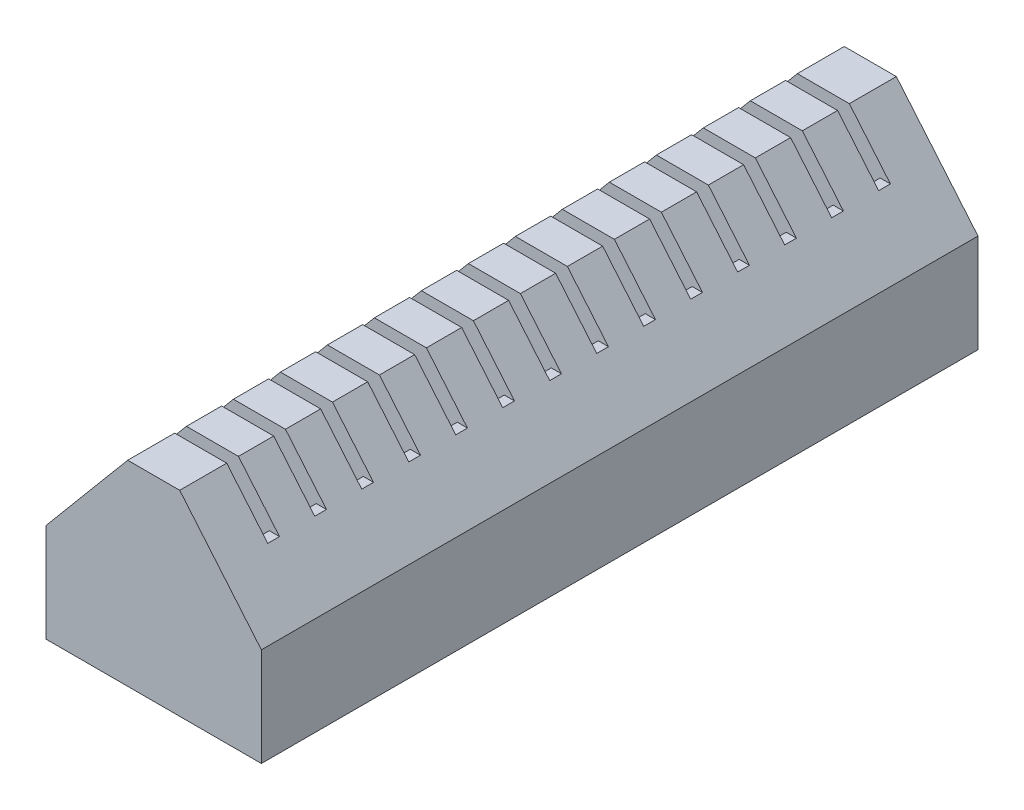
SolidWorks part; units mm, degrees
ref_plane "Ebene vorne" through (0, 0, 0) normal (0, 0, 1) x (1, 0, 0)
ref_plane "Ebene oben" through (0, 0, 0) normal (0, 1, 0) x (1, 0, 0)
ref_plane "Ebene rechts" through (0, 0, 0) normal (1, 0, 0) x (0, 0, -1)
sketch "Skizze3" plane through (0, 0, 0) normal (0, 0, 1) x (1, 0, 0)
  line L1 (0, 9.2) -> (0, -9.2) construction
  line L3 (-7.5, 0) -> (49992.5, 0) construction
  line L4 (-11, -3) -> (-11, 7.0579)
  line L5 (-11, 7.0579) -> (-2.6576, 17)
  line L6 (-2.6576, 17) -> (2.6576, 17)
  line L7 (2.6576, 17) -> (11, 7.0579)
  line L12 (0, 0) -> (8, 0) construction
  line L16 (11, 7.0579) -> (11, -3)
  line L18 (-11, -3) -> (11, -3)
  line L19 (8, 0) -> (8, 5.966) construction
  line L20 (8, 5.966) -> (0, 15.5) construction
  line L22 (0, 15.5) -> (-8, 5.966) construction
  line L23 (-8, 5.966) -> (-8, 0) construction
  line L24 (-8, 0) -> (0, 0) construction
  point P4 (0, 0)
  point P7 (0, 9.5114)
  point P16 (8.4307, 6.7411)
  point P19 (0, 0)
  point P20 (0, 15.4842)
  point P21 (0, 9.0697)
  point P23 (0, 0)
  point P24 (0, 15.6943)
  point P25 (11, 3)
  point P26 (0, 0)
  point P27 (11, 5.4655)
  point P28 (0, 0)
  dimension "D2" = 22
  dimension "D3" = 3
  dimension "D4" = 1.5
  dimension "D5" = 20
  dimension "D1" = 50
  dimension "D6" = 3
  dimension "D7" = 3
extrude "Aufsatz-Linear austragen2" add sketch "Skizze3" along normal mid plane 3.6
sketch "Skizze2" plane through (0, 0, 0) normal (0, 0, 1) x (1, 0, 0)
  line L1 (0, 9) -> (0, -9) construction
  line L3 (-7.5, 0) -> (49992.5, 0) construction
  line L20 (-8, 0) -> (8, 0)
  line L21 (8, 0) -> (8, 5.966)
  line L22 (8, 5.966) -> (1.2586, 14)
  line L23 (1.2586, 14) -> (-1.2586, 14)
  line L24 (-1.2586, 14) -> (-8, 5.966)
  line L25 (-8, 5.966) -> (-8, 0)
  line L26 (-8, 0) -> (8, 0)
  line L27 (8, 0) -> (8, 5.966)
  line L28 (8, 5.966) -> (0, 15.5)
  line L30 (0, 15.5) -> (-8, 5.966)
  line L31 (-8, 5.966) -> (-8, 0)
  point P2 (-0.7364, 14.6224)
  point P5 (0.7083, 14.6224)
  dimension "D1" = 3
extrude "Schnitt-Linear austragen1" cut sketch "Skizze2" against normal mid plane 1
sketch "Skizze5" plane through (0, 0, 0) normal (0, 0, 1) x (1, 0, 0)
  line L4 (-7.5519, 0) -> (-50007.5519, 0) construction
  line L5 (-8, 5.966) -> (-8, 0)
  line L6 (-8, 5.966) -> (-8, 0) construction
  line L7 (-8, 0) -> (8, 0)
  line L8 (-8, 0) -> (8, 0) construction
  line L9 (8, 0) -> (8, 5.966)
  line L15 (-0.75, 0) -> (0, 0.8938)
  line L16 (0, 0.8938) -> (0.75, 0)
  line L17 (0.75, 0) -> (-0.75, 0) construction
  line L18 (0, 0) -> (0, -50000) construction
  line L20 (8, 0) -> (8, 5.966) construction
  line L21 (8, 5.966) -> (0, 15.5)
  line L22 (8, 5.966) -> (0, 15.5) construction
  line L23 (0, 15.5) -> (-8, 5.966)
  line L24 (0, 15.5) -> (-8, 5.966) construction
  line L26 (-0.75, 0) -> (-0.75, -1.5)
  line L27 (-0.75, -1.5) -> (0.75, -1.5)
  line L28 (0.75, 0) -> (0.75, -1.5)
  dimension "D2" = 1.5
  dimension "D3" = 1.5
  dimension "D1" = 0
extrude "Schnitt-Linear austragen2" cut sketch "Skizze5" against normal through all both and the other way through all
sketch "Skizze6" plane through (0, 0, 1.8) normal (0, 0, 1) x (1, 0, 0)
  line L0 (0, 0) -> (0, -50000) construction
  line L1 (0, 0) -> (50000, 0) construction
  line L21 (-6.8531, 12) -> (-5.8087, 12)
  line L22 (-2.6576, 17) -> (-11, 7.0579) construction
  line L23 (-5.8087, 12) -> (-10.2, 6.7667)
  line L24 (-10.2, 6.7667) -> (-10.2, 2)
  line L25 (-10.2, 2) -> (10.2, 2)
  line L26 (0, 2) -> (0, -3) construction
  line L27 (-11, -3) -> (11, -3) construction
  line L28 (11, -3) -> (-11, -3)
  line L29 (-11, -3) -> (-11, 7.0579)
  line L30 (-11, 7.0579) -> (-6.8531, 12)
  line L31 (11, 7.0579) -> (6.8531, 12)
  line L32 (11, -3) -> (11, 7.0579)
  line L33 (10.2, 6.7667) -> (10.2, 2)
  line L34 (5.8087, 12) -> (10.2, 6.7667)
  line L35 (6.8531, 12) -> (5.8087, 12)
  line L36 (2.6576, 17) -> (-2.6576, 17) construction
  point P27 (-5.114, 13.1192)
  dimension "D1" = 0.8
  dimension "D2" = 0.8
  dimension "D3" = 2
  dimension "D4" = 5
extrude "Aufsatz-Linear austragen3" add sketch "Skizze6" along normal blind 1.2
pattern_linear "Lineares Muster1" count 15 spacing 4.8 along (0, 0, 1) of "Aufsatz-Linear austragen2", "Schnitt-Linear austragen1", "Schnitt-Linear austragen2", "Aufsatz-Linear austragen3"
sketch "Skizze8" plane through (0, 0, -1.8) normal (0, 0, -1) x (-1, 0, 0)
  line L9 (11, -3) -> (11, 7.0579)
  line L10 (11, 7.0579) -> (2.6576, 17)
  line L11 (2.6576, 17) -> (-2.6576, 17)
  line L12 (-2.6576, 17) -> (-11, 7.0579)
  line L13 (-11, 7.0579) -> (-11, -3)
  line L15 (-11, -3) -> (11, -3)
  line L17 (11, -3) -> (11, 7.0579)
  line L18 (11, 7.0579) -> (2.6576, 17)
  line L19 (2.6576, 17) -> (-2.6576, 17)
  line L20 (-2.6576, 17) -> (-11, 7.0579)
  line L21 (-11, 7.0579) -> (-11, -3)
  line L23 (-11, -3) -> (11, -3)
  dimension "D1" = 0
extrude "Aufsatz-Linear austragen4" add sketch "Skizze8" along normal blind 1.2 and the other way blind 1.3
sketch "Skizze9" plane through (0, 0, 69) normal (0, 0, 1) x (1, 0, 0)
  line L9 (-2.6576, 17) -> (-6.8531, 12)
  line L11 (-2.6576, 17) -> (-6.8531, 12)
  line L12 (-6.8531, 12) -> (-5.8087, 12)
  line L13 (-6.8531, 12) -> (-5.8087, 12)
  line L14 (-5.8087, 12) -> (-10.2, 6.7667)
  line L15 (-5.8087, 12) -> (-10.2, 6.7667)
  line L32 (-10.2, 6.7667) -> (-10.2, 2)
  line L33 (-10.2, 6.7667) -> (-10.2, 2)
  line L36 (-10.2, 2) -> (10.2, 2)
  line L37 (-10.2, 2) -> (10.2, 2)
  line L38 (10.2, 2) -> (10.2, 6.7667)
  line L39 (10.2, 2) -> (10.2, 6.7667)
  line L40 (10.2, 6.7667) -> (5.8087, 12)
  line L41 (10.2, 6.7667) -> (5.8087, 12)
  line L42 (5.8087, 12) -> (6.8531, 12)
  line L43 (5.8087, 12) -> (6.8531, 12)
  line L44 (6.8531, 12) -> (2.6576, 17)
  line L45 (6.8531, 12) -> (2.6576, 17)
  line L46 (2.6576, 17) -> (-2.6576, 17)
  line L47 (2.6576, 17) -> (-2.6576, 17)
  dimension "D1" = 0
extrude "Aufsatz-Linear austragen5" add sketch "Skizze9" along normal blind 1.2 and the other way blind 0.8
sketch "Skizze12" plane through (0, 0, 70.2) normal (0, 0, 1) x (1, 0, 0)
  line L8 (-0.75, -1.5) -> (-0.75, 0) construction
  line L9 (0.75, -1.5) -> (-0.75, -1.5) construction
  line L10 (0.75, 0) -> (0.75, -1.5) construction
  line L11 (0, 0.8938) -> (0.75, 0) construction
  line L12 (-0.75, 0) -> (0, 0.8938) construction
  line L13 (-0.75, -1.5) -> (-0.75, 0)
  line L14 (0.75, -1.5) -> (-0.75, -1.5)
  line L15 (0.75, 0) -> (0.75, -1.5)
  line L16 (0, 0.8938) -> (0.75, 0)
  line L17 (-0.75, 0) -> (0, 0.8938)
extrude "Aufsatz-Linear austragen7" add sketch "Skizze12" against normal up to vertex (3.5 mm away)
